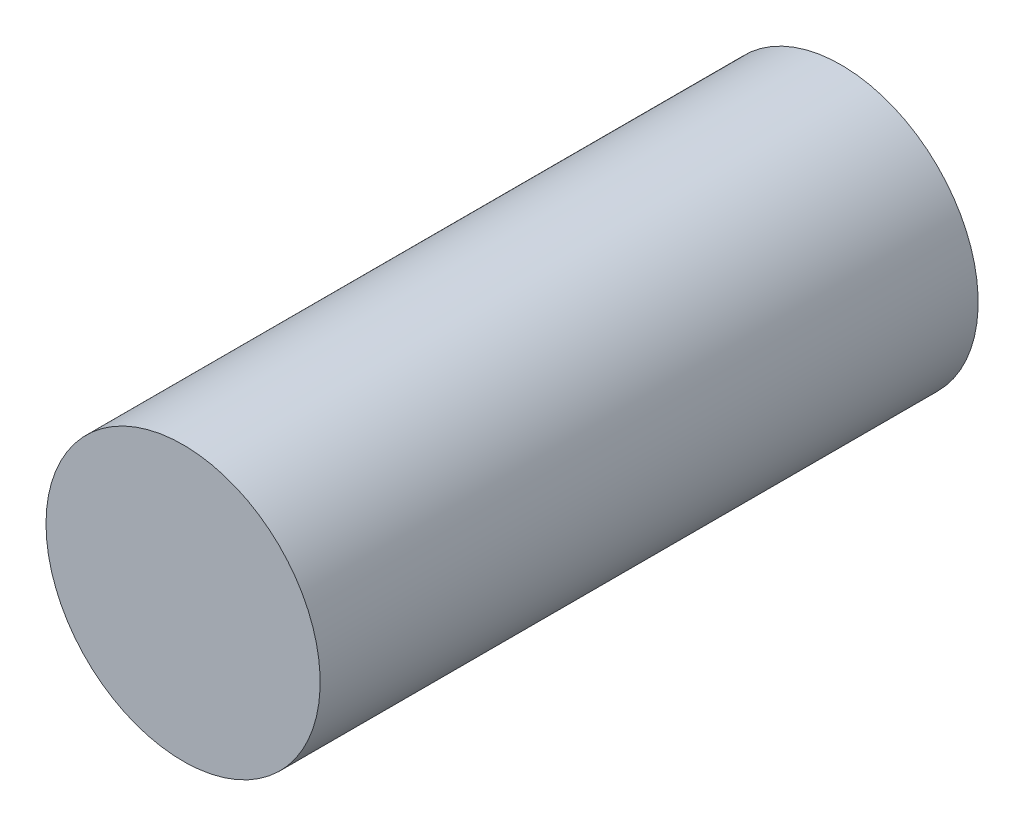
SolidWorks part; units mm, degrees
ref_plane "Front Plane" through (0, 0, 0) normal (0, 0, 1) x (1, 0, 0)
ref_plane "Top Plane" through (0, 0, 0) normal (0, 1, 0) x (1, 0, 0)
ref_plane "Right Plane" through (0, 0, 0) normal (1, 0, 0) x (0, 0, -1)
sketch "Sketch1" plane through (0, 0, 0) normal (0, 0, 1) x (1, 0, 0)
  circle A0 centre (-12.7409, 14.2322) radius 6.35
  dimension "D1" = 12.7
extrude "Boss-Extrude1" add sketch "Sketch1" along normal blind 30.48
